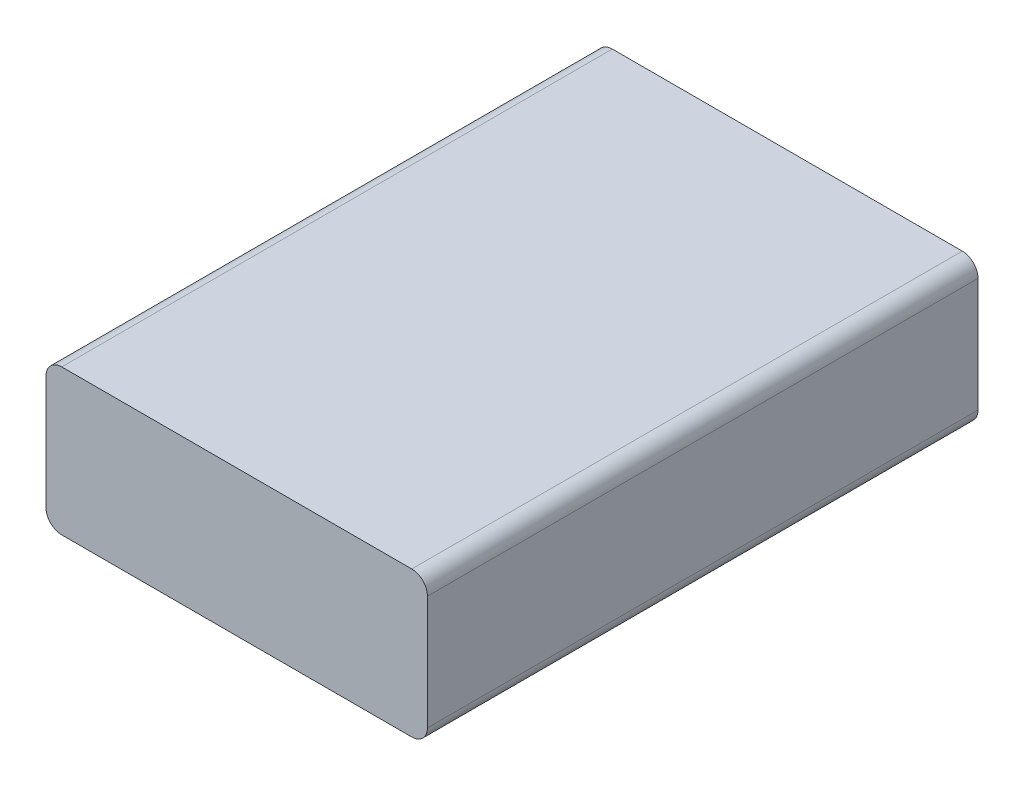
SolidWorks part; units mm, degrees
material "Malleable Cast Iron"
ref_plane "Front Plane" through (0, 0, 0) normal (0, 0, 1) x (1, 0, 0)
ref_plane "Top Plane" through (0, 0, 0) normal (0, 1, 0) x (1, 0, 0)
ref_plane "Right Plane" through (0, 0, 0) normal (1, 0, 0) x (0, 0, -1)
sketch "Sketch1" plane through (0, 0, 0) normal (0, 1, 0) x (1, 0, 0)
  line L1 (-24.25, -35) -> (24.25, -35)
  line L2 (-24.25, -35) -> (-24.25, 35)
  line L3 (-24.25, 35) -> (24.25, 35)
  line L4 (24.25, -35) -> (24.25, 35)
  line L5 (-24.25, -35) -> (24.25, 35) construction
  line L6 (-24.25, 35) -> (24.25, -35) construction
  point P0 (0, 0)
  dimension "D1" = 70
  dimension "D2" = 48.5
extrude "Boss-Extrude1" add sketch "Sketch1" along normal blind 18.5
fillet "Fillet1" radius 2 4 edges at (-24.25, 0, 0) (24.25, 0, 0) (-24.25, 18.5, 0) (24.25, 18.5, 0)
